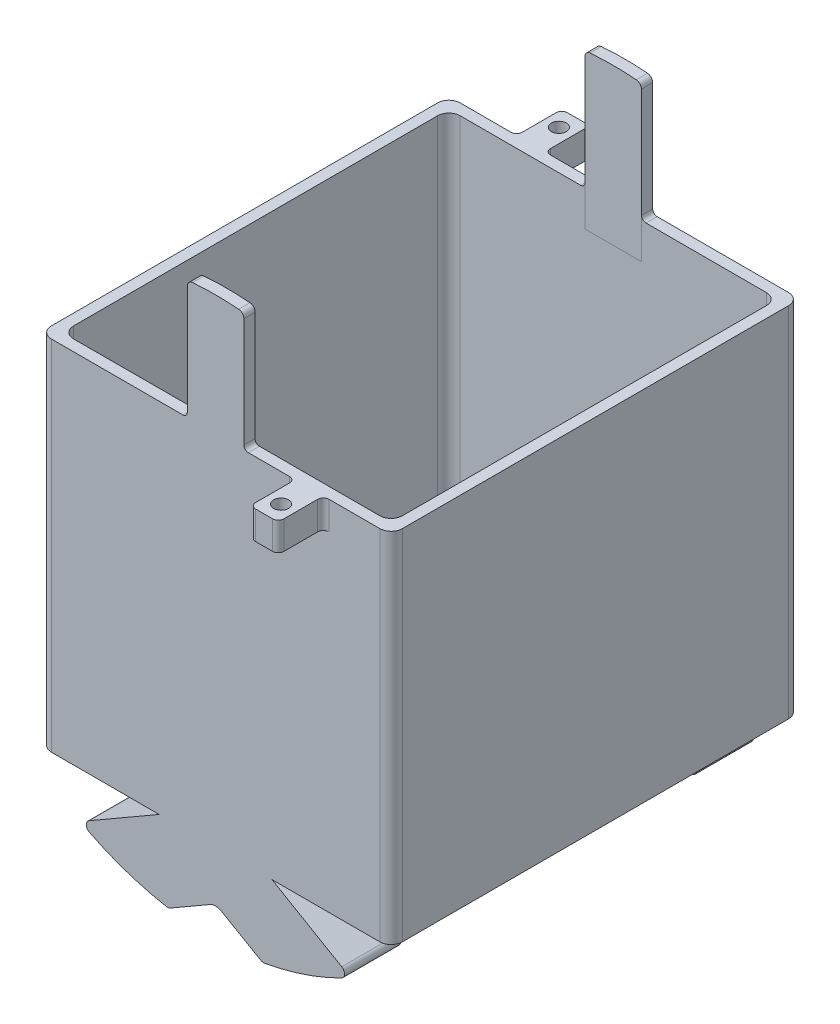
SolidWorks part; units mm, degrees
ref_plane "Front Plane" through (0, 0, 0) normal (0, 0, 1) x (1, 0, 0)
ref_plane "Top Plane" through (0, 0, 0) normal (0, 1, 0) x (1, 0, 0)
ref_plane "Right Plane" through (0, 0, 0) normal (1, 0, 0) x (0, 0, -1)
sketch "Sketch1" plane through (0, 0, 0) normal (0, 1, 0) x (1, 0, 0)
  line L1 (-36.96, -46) -> (36.96, -46)
  line L2 (-39.5, -43.46) -> (-39.5, 43.46)
  line L3 (-36.96, 46) -> (36.96, 46)
  line L4 (39.5, -43.46) -> (39.5, 43.46)
  line L5 (-39.5, -46) -> (39.5, 46) construction
  line L6 (-39.5, 46) -> (39.5, -46) construction
  arc A0 (-36.96, -46) -> (-39.5, -43.46) centre (-36.96, -43.46) cw
  arc A1 (36.96, -46) -> (39.5, -43.46) centre (36.96, -43.46) ccw
  arc A2 (36.96, 46) -> (39.5, 43.46) centre (36.96, 43.46) cw
  arc A3 (-39.5, 43.46) -> (-36.96, 46) centre (-36.96, 43.46) cw
  point P0 (0, 0)
  dimension "D3" = 2.54
  dimension "D1" = 92
  dimension "D2" = 79
extrude "Boss-Extrude1" add sketch "Sketch1" against normal blind 70 contours L1 A1 L4 A2 L3 A3 L2 A0
sketch "Sketch2" plane through (0, 0, 0) normal (0, 1, 0) x (1, 0, 0)
  line L6 (-34.46, -43.5) -> (34.46, -43.5)
  line L7 (-37, -40.96) -> (-37, 40.96)
  line L8 (-34.46, 43.5) -> (34.46, 43.5)
  line L9 (37, -40.96) -> (37, 40.96)
  line L10 (-37, -43.5) -> (37, 43.5) construction
  line L11 (-37, 43.5) -> (37, -43.5) construction
  arc A0 (-34.46, -43.5) -> (-37, -40.96) centre (-34.46, -40.96) cw
  arc A1 (34.46, -43.5) -> (37, -40.96) centre (34.46, -40.96) ccw
  arc A2 (34.46, 43.5) -> (37, 40.96) centre (34.46, 40.96) cw
  arc A3 (-37, 40.96) -> (-34.46, 43.5) centre (-34.46, 40.96) cw
  point P0 (0, 0)
  dimension "D2" = 87
  dimension "D3" = 2.54
  dimension "D1" = 74
extrude "Cut-Extrude1" cut sketch "Sketch2" against normal blind 79.756 contours L7 A3 L8 A2 L9 A1 L6 A0
sketch "Sketch3" plane through (0, 0, 0) normal (0, 1, 0) x (1, 0, 0)
  line L0 (0, 47.5218) -> (0, -50.955)
  line L1 (-44.9266, 0) -> (39.5, 0)
  line L2 (39.5, -43.46) -> (39.5, 43.46) construction
  line L4 (39.5, -3.175) -> (39.5, 3.175)
  line L5 (39.5, 3.175) -> (49.66, 3.175)
  line L6 (49.66, -3.175) -> (49.66, 3.175)
  line L7 (39.5, -3.175) -> (49.66, -3.175)
  line L9 (39.5, 0) -> (49.66, 0)
  line L10 (-39.5, -3.175) -> (-39.5, 3.175)
  line L11 (-39.5, 3.175) -> (-49.66, 3.175)
  line L12 (-49.66, -3.175) -> (-49.66, 3.175)
  line L13 (-39.5, -3.175) -> (-49.66, -3.175)
  circle A0 centre (45.85, 0) radius 1.5
  circle A1 centre (-45.85, 0) radius 1.5
  dimension "D2" = 3
  dimension "D1" = 10.16
  dimension "D3" = 6.35
  dimension "D4" = 3.81
sketch "Sketch4" plane through (0, -70, 0) normal (0, -1, 0) x (1, 0, 0)
  line L9 (-36.96, -46) -> (36.96, -46) construction
  line L10 (36.96, 46) -> (-36.96, 46)
  line L11 (39.5, 43.46) -> (39.5, -43.46)
  line L12 (36.96, -46) -> (-36.96, -46)
  line L13 (-39.5, 43.46) -> (-39.5, -43.46)
  line L14 (39.5, 46) -> (-39.5, -46) construction
  line L15 (39.5, -46) -> (-39.5, 46) construction
  line L16 (-39.5, 43.46) -> (-39.5, -43.46) construction
  arc A4 (36.96, 46) -> (39.5, 43.46) centre (36.96, 43.46) cw
  arc A5 (-36.96, 46) -> (-39.5, 43.46) centre (-36.96, 43.46) ccw
  arc A6 (-36.96, -46) -> (-39.5, -43.46) centre (-36.96, -43.46) cw
  arc A7 (39.5, -43.46) -> (36.96, -46) centre (36.96, -43.46) cw
  point P0 (0, 0)
  dimension "D1" = 2.54
extrude "Boss-Extrude3" add sketch "Sketch4" along normal blind 2.54
sketch "Sketch5" plane through (0, 0, 46) normal (0, 0, 1) x (1, 0, 0)
  line L5 (0, 0) -> (0, -171.6808) construction
  line L6 (-12.7, -72.54) -> (-28.4536, -81.6354)
  line L7 (36.96, -72.54) -> (-36.96, -72.54) construction
  line L8 (0, 0) -> (0, -78.1077)
  line L9 (51.6986, -36.6701) -> (-47.1831, -36.6701)
  line L11 (-10.1667, -89.5204) -> (-1.2701, -84.384)
  line L18 (12.7, -72.54) -> (28.3836, -81.6753)
  line L20 (10.1657, -89.5206) -> (1.27, -84.384)
  line L21 (-12.7, -72.54) -> (12.7, -72.54)
  line L23 (6.3629, 0) -> (-6.3629, 0)
  line L27 (6.3629, 0) -> (6.3629, 33.604)
  line L28 (6.3629, 0) -> (-6.3629, 0)
  line L31 (-6.3629, 0) -> (-6.3629, 33.604)
  arc A0 (1.27, -84.384) -> (-1.2701, -84.384) centre (-0.0001, -86.5837) ccw
  arc A8 (-28.3922, -83.8683) -> (-11.0244, -89.6709) centre (0, -27.7801) ccw
  arc A9 (5.1979, 34.8697) -> (-5.1979, 34.8697) centre (0, -27.7801) ccw
  arc A10 (11.0235, -89.6711) -> (28.3165, -83.9066) centre (0, -27.7801) ccw
  arc A11 (6.3629, 33.604) -> (5.1979, 34.8697) centre (5.0929, 33.604) ccw
  arc A12 (-5.1979, 34.8697) -> (-6.3629, 33.604) centre (-5.0929, 33.604) ccw
  arc A13 (-10.1667, -89.5204) -> (-11.0244, -89.6709) centre (-10.8017, -88.4206) cw
  arc A14 (10.1657, -89.5206) -> (11.0235, -89.6711) centre (10.8008, -88.4207) ccw
  arc A15 (28.3836, -81.6753) -> (28.3165, -83.9066) centre (27.7444, -82.7727) cw
  arc A16 (-28.4536, -81.6354) -> (-28.3922, -83.8683) centre (-27.8186, -82.7352) ccw
  point P13 (0, -36.6701)
  point P19 (0, -83.6507)
  point P22 (6.3629, 34.7621)
  point P28 (-6.3629, 34.7621)
  point P33 (10.5648, -89.751)
  dimension "D4" = 2.54
  dimension "D3" = 125.73
  dimension "D5" = 1.27
  dimension "D1" = 25.4
  dimension "D2" = 60
  dimension "D6" = 8.89
extrude "Boss-Extrude4" add sketch "Sketch5" against normal blind 2.54 contours L28 L31 A12 A9 A11 L27
extrude "Boss-Extrude5" add sketch "Sketch5<4>" against normal blind 12.7 contours L11 A0 L20 A14 A10 A15 L18 L21 L6 A16 A8 A13
sketch "Sketch5<4>" plane through (0, 0, 46) normal (0, 0, 1) x (1, 0, 0) same geometry as "Sketch5"
sketch "Sketch6" plane through (0, 0, -46) normal (0, 0, -1) x (-1, 0, 0)
  line L0 (0, 45.6978) -> (0, -113.8885)
  line L5 (-51.6986, -36.6701) -> (47.1831, -36.6701)
  line L6 (-12.7, -72.54) -> (12.7, -72.54)
  line L7 (12.7, -72.54) -> (28.4536, -81.6354)
  line L8 (10.1667, -89.5204) -> (1.2701, -84.384)
  line L9 (-1.27, -84.384) -> (-10.1657, -89.5206)
  line L10 (-28.3836, -81.6753) -> (-12.7, -72.54)
  line L14 (-6.3629, 0) -> (-6.3629, 33.604)
  line L15 (6.3629, 33.604) -> (6.3629, 0)
  line L16 (6.3629, 0) -> (-6.3629, 0)
  arc A0 (28.4536, -81.6354) -> (28.3922, -83.8683) centre (27.8186, -82.7352) cw
  arc A1 (28.3922, -83.8683) -> (11.0244, -89.6709) centre (0, -27.7801) cw
  arc A2 (11.0244, -89.6709) -> (10.1667, -89.5204) centre (10.8017, -88.4206) cw
  arc A3 (1.2701, -84.384) -> (-1.27, -84.384) centre (0.0001, -86.5837) ccw
  arc A4 (-10.1657, -89.5206) -> (-11.0235, -89.6711) centre (-10.8008, -88.4207) cw
  arc A5 (-11.0235, -89.6711) -> (-28.3165, -83.9066) centre (0, -27.7801) cw
  arc A6 (-28.3165, -83.9066) -> (-28.3836, -81.6753) centre (-27.7444, -82.7727) cw
  arc A10 (-6.3629, 33.604) -> (-5.1979, 34.8697) centre (-5.0929, 33.604) cw
  arc A11 (-5.1979, 34.8697) -> (5.1979, 34.8697) centre (0, -27.7801) cw
  arc A12 (5.1979, 34.8697) -> (6.3629, 33.604) centre (5.0929, 33.604) cw
extrude "Boss-Extrude6" add sketch "Sketch6" against normal blind 2.54 contours L16 L14 A10 A11 A12 L15
extrude "Boss-Extrude7" add sketch "Sketch6<3>" against normal blind 12.7 contours L9 A4 A5 A6 L10 L6 L7 A0 A1 A2 L8 A3
sketch "Sketch6<3>" plane through (0, 0, -46) normal (0, 0, -1) x (-1, 0, 0) same geometry as "Sketch6"
sketch "Sketch8" plane through (0, 0, 0) normal (0, 1, 0) x (1, 0, 0)
  line L0 (6.3629, -46) -> (6.3629, -43.46)
  line L1 (6.3629, -43.46) -> (34.46, -43.5)
  line L2 (37, -40.96) -> (37, 40.96)
  line L4 (-37, 40.96) -> (-37, -40.96)
  line L7 (39.5, 43.46) -> (39.5, -43.46)
  line L8 (36.96, -46) -> (6.3629, -46)
  line L9 (0, -73.8832) -> (0, 63.9189) construction
  line L10 (-36.96, -46) -> (-6.3629, -46)
  line L11 (-39.5, 43.46) -> (-39.5, -43.46)
  line L12 (-6.3629, 46) -> (-36.96, 46)
  line L13 (-6.3629, 43.5) -> (-6.3629, 46)
  line L14 (-34.46, 43.5) -> (-6.3629, 43.5)
  line L15 (-37, -40.96) -> (-37, 40.96)
  line L16 (-34.46, -43.5) -> (-6.3629, -43.46)
  line L17 (-6.3629, -46) -> (-6.3629, -43.46)
  line L18 (34.46, 43.5) -> (6.3629, 43.5)
  line L19 (6.3629, 43.5) -> (6.3629, 46)
  line L20 (6.3629, 46) -> (36.96, 46)
  arc A0 (34.46, -43.5) -> (37, -40.96) centre (34.4636, -40.9636) ccw
  arc A1 (37, 40.96) -> (34.46, 43.5) centre (34.46, 40.96) ccw
  arc A2 (-34.46, 43.5) -> (-37, 40.96) centre (-34.46, 40.96) ccw
  arc A3 (-34.46, 43.5) -> (-37, 40.96) centre (-34.46, 40.96) ccw construction
  arc A4 (-34.46, 43.5) -> (-37, 40.96) centre (-34.46, 40.96) ccw construction
  arc A5 (36.96, 46) -> (39.5, 43.46) centre (36.96, 43.46) cw
  arc A6 (39.5, -43.46) -> (36.96, -46) centre (36.96, -43.46) cw
  arc A7 (-39.5, -43.46) -> (-36.96, -46) centre (-36.96, -43.46) ccw
  arc A8 (-36.96, 46) -> (-39.5, 43.46) centre (-36.96, 43.46) ccw
  arc A9 (-37, 40.96) -> (-34.46, 43.5) centre (-34.46, 40.96) cw
  arc A10 (-34.46, -43.5) -> (-37, -40.96) centre (-34.4636, -40.9636) cw
  line M4 (6.3629, 43.5) -> (34.46, 43.5)
  arc M5 (34.46, 43.5) -> (37, 40.96) centre (34.46, 40.96) cw
  line M6 (37, 40.96) -> (37, -40.96)
  line M8 (34.46, -43.5) -> (6.3629, -43.5)
  line M9 (6.3629, -43.5) -> (6.3629, -46)
  line M10 (6.3629, -46) -> (36.96, -46)
  arc M11 (36.96, -46) -> (39.5, -43.46) centre (36.96, -43.46) ccw
  line M12 (39.5, -43.46) -> (39.5, 43.46)
  line M20 (39.5, -43.46) -> (39.5, 43.46)
  arc M21 (39.5, 43.46) -> (36.96, 46) centre (36.96, 43.46) ccw
  line M22 (36.96, 46) -> (6.3629, 46)
extrude "Boss-Extrude8" add sketch "Sketch8" along normal blind 8 contours A0 L7 M8 M9 M10 M11 M12 M20 M21 M22 M4 M5 M6 | L16 A10 L4 A2 L14 L13 L12 A8 L11 A7 L10 L17 region at (7.3407, 0, 44.75) region at (-37.9779, 0, 0)
sketch "Sketch9" plane through (0, 8, 0) normal (0, 1, 0) x (1, 0, 0)
  line L4 (-65.6619, 0) -> (90.975, 0) construction
  line L6 (0, -59.3305) -> (0, 73.3676) construction
  line L7 (-36.96, -46) -> (-6.3629, -46) construction
  line L8 (-17.91, 46) -> (-17.91, 54.89)
  line L9 (-24.26, -46) -> (-17.91, -46)
  line L10 (-24.26, -46) -> (-24.26, -54.89)
  line L11 (-22.99, -56.16) -> (-19.18, -56.16)
  line L12 (-17.91, -46) -> (-17.91, -54.89)
  line L13 (-22.99, 56.16) -> (-19.18, 56.16)
  line L14 (-24.26, 46) -> (-24.26, 54.89)
  line L15 (-24.26, 46) -> (-17.91, 46)
  line L16 (24.26, 46) -> (17.91, 46)
  line L17 (24.26, 46) -> (24.26, 54.89)
  line L18 (22.99, 56.16) -> (19.18, 56.16)
  line L19 (17.91, 46) -> (17.91, 54.89)
  line L20 (17.91, -46) -> (17.91, -54.89)
  line L21 (22.99, -56.16) -> (19.18, -56.16)
  line L22 (24.26, -46) -> (24.26, -54.89)
  line L23 (24.26, -46) -> (17.91, -46)
  line L24 (-39.5, 43.46) -> (-39.5, -43.46) construction
  circle A1 centre (-21.085, -52.35) radius 1.6852
  arc A2 (-19.18, -56.16) -> (-17.91, -54.89) centre (-19.18, -54.89) ccw
  arc A3 (-24.26, -54.89) -> (-22.99, -56.16) centre (-22.99, -54.89) ccw
  arc A4 (-24.26, 54.89) -> (-22.99, 56.16) centre (-22.99, 54.89) cw
  arc A5 (-19.18, 56.16) -> (-17.91, 54.89) centre (-19.18, 54.89) cw
  circle A6 centre (-21.085, 52.35) radius 1.6852
  circle A7 centre (21.085, 52.35) radius 1.6852
  arc A8 (19.18, 56.16) -> (17.91, 54.89) centre (19.18, 54.89) ccw
  arc A9 (24.26, 54.89) -> (22.99, 56.16) centre (22.99, 54.89) ccw
  arc A10 (24.26, -54.89) -> (22.99, -56.16) centre (22.99, -54.89) cw
  arc A11 (19.18, -56.16) -> (17.91, -54.89) centre (19.18, -54.89) cw
  circle A12 centre (21.085, -52.35) radius 1.6852
  point P20 (-17.91, -56.16)
  point P23 (-24.26, -56.16)
  point P31 (-24.26, 56.16)
  point P32 (-17.91, 56.16)
  point P43 (17.91, 56.16)
  point P44 (24.26, 56.16)
  point P55 (24.26, -56.16)
  point P56 (17.91, -56.16)
  line M15 (-6.3629, 46) -> (-36.96, 46)
  dimension "D2" = 15.24
  dimension "D10" = 1.27
  dimension "D5" = 6.35
  dimension "D6" = 10.16
  dimension "D7" = 3.175
  dimension "D8" = 3.81
extrude "Boss-Extrude9" add sketch "Sketch9" against normal blind 6.35 contours A5 L13 A4 L14 L8 A6 M15 | L22 A10 L21 A11 L20 L23 | A12 region at (-21.085, 8, -46.1198)
fillet "Fillet1" radius 1.27 4 edges at (-24.26, 4.825, -46) (-17.91, 4.825, -46) (17.91, 4.825, 46) (24.26, 4.825, 46)
fillet "Fillet3" radius 1 4 edges at (-6.3629, 8, 44.73) (6.3629, 8, 44.75) (6.3629, 8, -44.75) (-6.3629, 8, -44.75)
